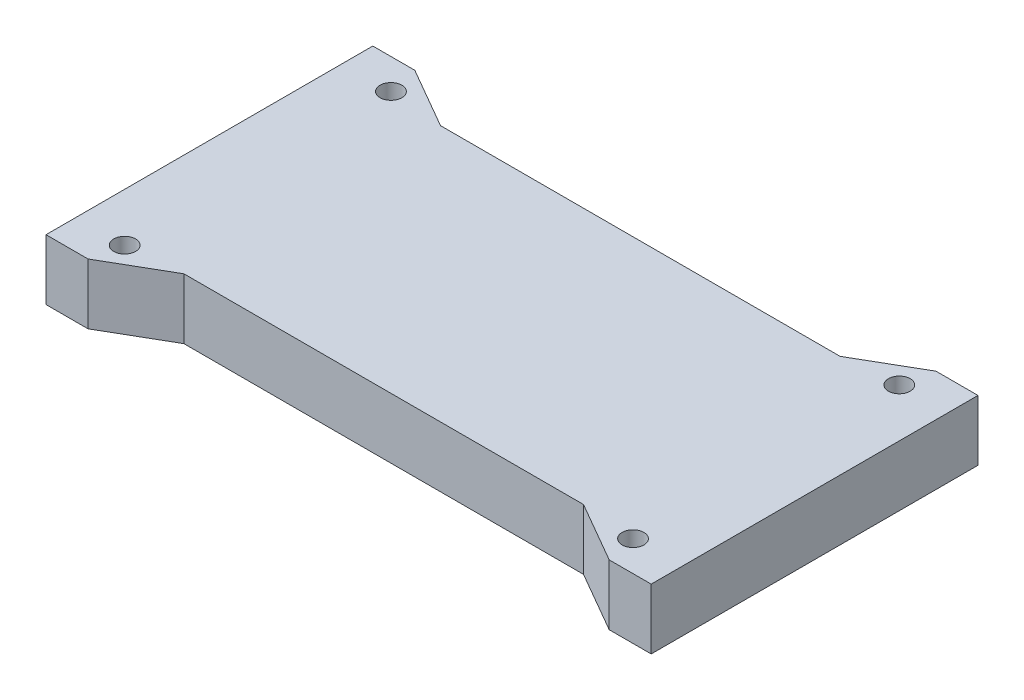
SolidWorks part; units mm, degrees
ref_plane "Front Plane" through (0, 0, 0) normal (0, 0, 1) x (1, 0, 0)
ref_plane "Top Plane" through (0, 0, 0) normal (0, 1, 0) x (1, 0, 0)
ref_plane "Right Plane" through (0, 0, 0) normal (1, 0, 0) x (0, 0, -1)
sketch "Sketch1" plane through (0, 0, 0) normal (0, 1, 0) x (1, 0, 0)
  line L0 (0, 0) -> (9.0185, 0) construction
  line L1 (-42, -22) -> (42, -22) construction
  line L2 (-42, -22) -> (-42, 22) construction
  line L3 (-42, 22) -> (42, 22) construction
  line L4 (42, -22) -> (42, 22) construction
  line L5 (-42, -22) -> (42, 22) construction
  line L6 (-42, 22) -> (42, -22) construction
  line L7 (0, 0) -> (0, 72.303) construction
  line L8 (50, 27) -> (43.0603, 27)
  line L9 (-50, -25) -> (50, -25)
  line L10 (-50, -25) -> (-50, 25)
  line L11 (-50, 25) -> (50, 25)
  line L12 (50, -25) -> (50, 25)
  line L13 (-50, -25) -> (50, 25) construction
  line L14 (-50, 25) -> (50, -25) construction
  line L15 (58.1438, 20.2) -> (0, 20.2) construction
  line L16 (-33.0144, 21.2) -> (33.0144, 21.2)
  line L17 (33.0144, 21.2) -> (43.0603, 27)
  line L18 (35.2823, 20.2) -> (56.3152, 32.3434) construction
  line L19 (50, 25) -> (50, 27)
  line L20 (-50, 25) -> (-50, 27)
  line L21 (-50, 27) -> (-43.0603, 27)
  line L22 (-33.0144, 21.2) -> (-43.0603, 27)
  line L23 (50, -25) -> (50, -27)
  line L24 (50, -27) -> (43.0603, -27)
  line L25 (33.0144, -21.2) -> (43.0603, -27)
  line L26 (-33.0144, -21.2) -> (33.0144, -21.2)
  line L27 (-33.0144, -21.2) -> (-43.0603, -27)
  line L28 (-50, -27) -> (-43.0603, -27)
  line L29 (-50, -25) -> (-50, -27)
  line L30 (0, 21.2) -> (0, 25)
  line L31 (0, -21.2) -> (0, -25)
  circle A0 centre (42, 22) radius 1.8
  circle A1 centre (-42, 22) radius 1.8
  circle A2 centre (-42, -22) radius 1.8
  circle A3 centre (42, -22) radius 1.8
  point P0 (0, 0)
  point P34 (0, 21.2)
  dimension "D3" = 3.6
  dimension "D1" = 44
  dimension "D2" = 84
  dimension "D4" = 8
  dimension "D5" = 3
  dimension "D6" = 1
  dimension "D7" = 30
  dimension "D8" = 2
  dimension "D9" = 2
extrude "Boss-Extrude2" add sketch "Sketch1" along normal blind 10 contours L27 L26 L25 L9 L12 L11 L17 L16 L22 L10 A1 A0 A2 A3 region at (0, 0, 0)
extrude "Boss-Extrude3" add sketch "Sketch1<4>" along normal up to surface (10 mm away) contours L11 L19 L8 L17 region at (45.6064, 0, -25.9334) up to face at (-42, 10, -20.2)
sketch "Sketch1<4>" plane through (0, 0, 0) normal (0, 1, 0) x (1, 0, 0) same geometry as "Sketch1"
mirror "Mirror1" about plane through (0, 0, 0) normal (0, 0, 1) of "Boss-Extrude3" second plane through (0, 0, 0) second plane normal (1, 0, 0)
sketch "Sketch2" plane through (0, 0, 0) normal (1, 0, 0) x (0, 0, -1)
  line L0 (0, -30) -> (9.8369, -30)
  line L1 (12, -30) -> (32.3221, 10.6441) construction
  line L2 (0, 0) -> (0, 31.9272) construction
  line L3 (25, 0) -> (-25, 0) construction
  line L4 (-200000, 0) -> (200072.303, 0) construction
  line L5 (27, 0) -> (12.9674, -28.0652)
  arc A0 (9.8369, -30) -> (12.9674, -28.0652) centre (9.8369, -26.5) ccw
  point P12 (0, 0)
  point P14 (12, -30)
  point P15 (12, -30)
  point P16 (11.9019, -31.531)
  point P18 (0, 0)
  point P19 (0, 0)
  point P20 (27, 0)
  point P22 (32.3221, 10.6441)
  dimension "D3" = 3.5
  dimension "D1" = 30
  dimension "D2" = 12
